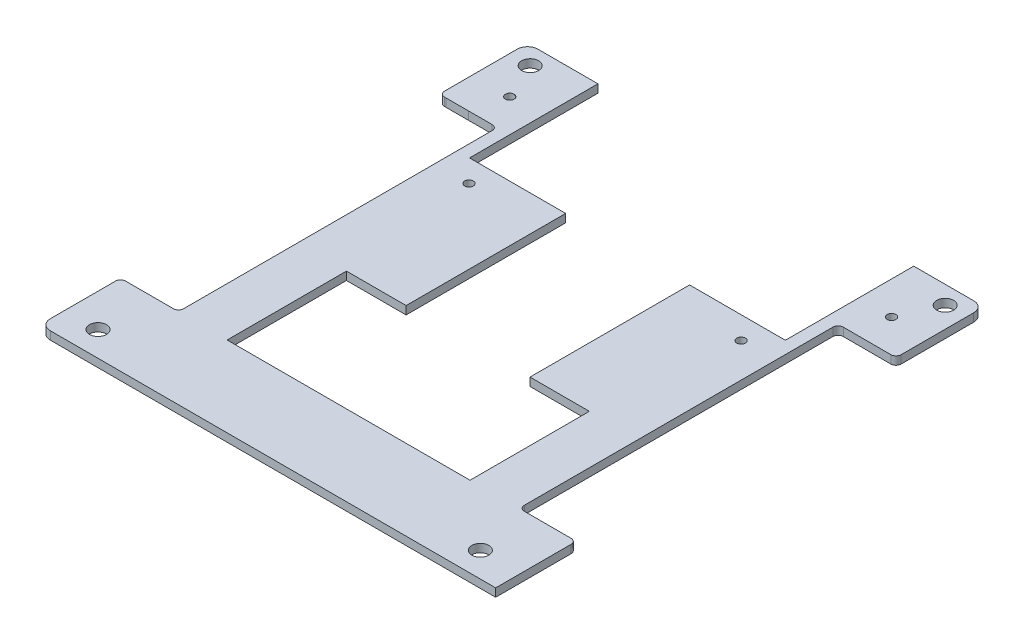
SolidWorks part; units mm, degrees
material "Copper"
ref_plane "Front Plane" through (0, 0, 0) normal (0, 0, 1) x (1, 0, 0)
ref_plane "Top Plane" through (0, 0, 0) normal (0, 1, 0) x (1, 0, 0)
ref_plane "Right Plane" through (0, 0, 0) normal (1, 0, 0) x (0, 0, -1)
sketch "Sketch1" plane through (0, 0, 0) normal (0, 1, 0) x (1, 0, 0)
  line L0 (-38.395, 30) -> (-42.73, 30)
  line L1 (-44, 31.27) -> (-44, 45)
  line L2 (42, 47) -> (30.435, 47)
  line L3 (44, 45) -> (44, 32)
  line L4 (44, 32) -> (44, 31.0156)
  line L5 (42.9984, 30.0156) -> (33.8256, 30.0304)
  line L6 (32.824, 29.0304) -> (32.824, -30.454)
  line L7 (-44, -38.977) -> (-44, -32.454)
  line L8 (-42, -47) -> (43.8497, -47)
  line L9 (-44, -45) -> (-44, -38.977)
  line L10 (-43, -31.454) -> (-36.1, -31.454)
  line L11 (43.8497, -37) -> (43.8497, -32.454)
  line L12 (42.8497, -31.454) -> (36.1, -31.454)
  line L13 (23.409, -31.5) -> (-23.409, -31.5)
  line L14 (-11.909, -8.5) -> (-23.409, -8.5)
  line L15 (30.435, 22.2554) -> (11.9708, 22.2554)
  line L16 (-11.909, -8.5) -> (-11.909, 22.2554)
  line L17 (30.435, 47) -> (30.435, 22.2554)
  line L18 (11.9708, 22.2554) -> (11.9708, -8.5)
  line L19 (-23.409, -31.5) -> (-23.409, -8.5)
  line L20 (11.9708, -8.5) -> (23.409, -8.5)
  line L21 (-36.1, -31.454) -> (-33.824, -31.454)
  line L22 (-32.824, -30.454) -> (-32.824, 29.0115)
  line L23 (-33.8265, 30.0115) -> (-38.395, 30)
  line L24 (-42.73, 30) -> (-43.011, 30.0031)
  line L25 (-44, 31.003) -> (-44, 31.27)
  line L28 (43.8497, -47) -> (43.8497, -37)
  line L33 (33.824, -31.454) -> (36.1, -31.454)
  line L34 (-23.409, 13.2954) -> (-23.409, -31.5) construction
  line L35 (23.409, -31.5) -> (23.409, -8.5)
  line L41 (-42, 47) -> (-30.435, 47)
  line L42 (-30.435, 47) -> (-30.435, 22.2554)
  line L43 (-30.435, 22.2554) -> (-11.909, 22.2554)
  circle A0 centre (40, 43.5) radius 1.6383
  circle A1 centre (-40, 43.5) radius 1.6383
  circle A2 centre (-37.6, -42.2) radius 1.6383
  circle A3 centre (36.1, -42.2) radius 1.6383
  circle A4 centre (-36.785, 36.35) radius 0.8382
  arc A5 (-42, 47) -> (-44, 45) centre (-42, 45) ccw
  arc A6 (44, 45) -> (42, 47) centre (42, 45) ccw
  circle A7 centre (-26.22, 17.9319) radius 0.8382
  circle A8 centre (26.22, 17.9319) radius 0.8382
  arc A9 (-43.011, 30.0031) -> (-44, 31.003) centre (-43, 31.003) cw
  arc A10 (-32.824, 29.0115) -> (-33.8265, 30.0115) centre (-33.824, 29.0115) ccw
  arc A11 (-44, -45) -> (-42, -47) centre (-42, -45) ccw
  arc A12 (44, 31.0156) -> (42.9984, 30.0156) centre (43, 31.0156) cw
  circle A13 centre (36.785, 36.368) radius 0.8382
  arc A14 (33.8256, 30.0304) -> (32.824, 29.0304) centre (33.824, 29.0304) ccw
  arc A15 (43.8497, -32.454) -> (42.8497, -31.454) centre (42.8497, -32.454) ccw
  arc A16 (32.824, -30.454) -> (33.824, -31.454) centre (33.824, -30.454) ccw
  arc A17 (-33.824, -31.454) -> (-32.824, -30.454) centre (-33.824, -30.454) ccw
  arc A18 (-44, -32.454) -> (-43, -31.454) centre (-43, -32.454) cw
  point P37 (-44, 30.014)
  point P48 (-32.824, 30.014)
  point P61 (44, 30.014)
  point P80 (32.824, 30.032)
  point P95 (32.824, -31.454)
  point P98 (-32.824, -31.454)
  dimension "D1" = 1
  dimension "D2" = 73.7
  dimension "D3" = 85.7
  dimension "D4" = 80
  dimension "D5" = 85.7
extrude "Boss-Extrude1" [suppressed] add sketch "Sketch1" along normal blind 1.575
extrude "Boss-Extrude2" add sketch "Sketch1<2>" along normal blind 1.575
sketch "Sketch1<2>" plane through (0, 0, 0) normal (0, 1, 0) x (1, 0, 0) same geometry as "Sketch1"
